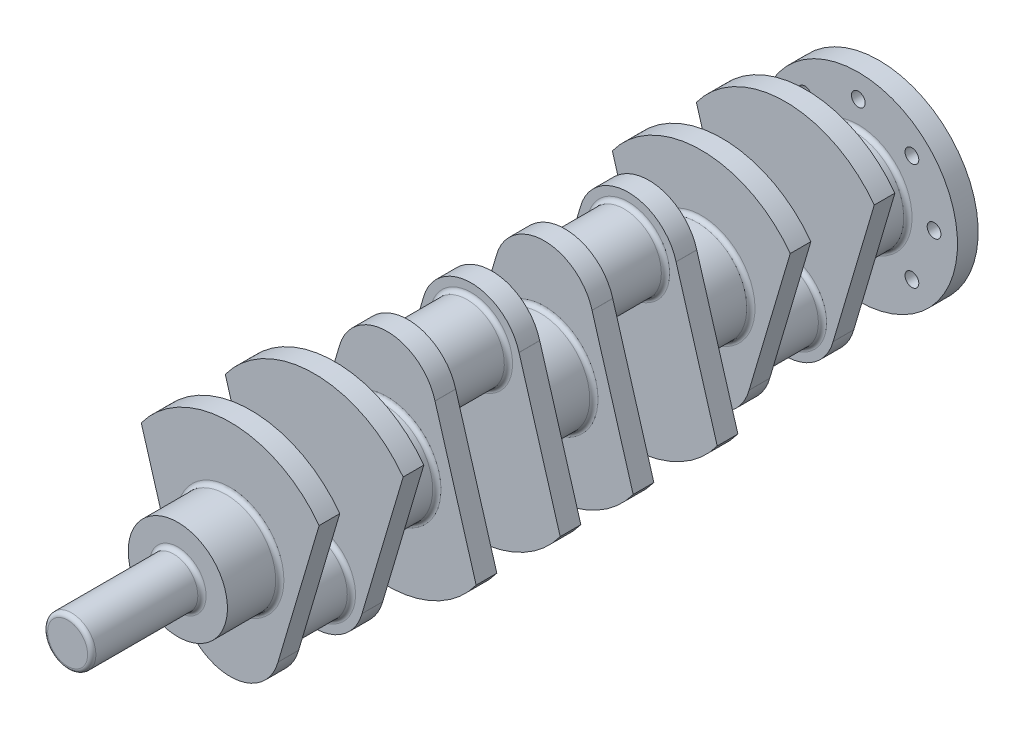
SolidWorks part; units mm, degrees
ref_plane "Front Plane" through (0, 0, 0) normal (0, 0, 1) x (1, 0, 0)
ref_plane "Top Plane" through (0, 0, 0) normal (0, 1, 0) x (1, 0, 0)
ref_plane "Right Plane" through (0, 0, 0) normal (1, 0, 0) x (0, 0, -1)
sketch "Sketch1" plane through (0, 0, 0) normal (0, 0, 1) x (1, 0, 0)
  line L0 (-840.1936, 0) -> (783.1901, 0) construction
  line L1 (0, 0) -> (0, -1117.6) construction
  line L2 (0, 0) -> (0, 1246.1176) construction
  line L3 (-1639.9655, 1199.8071) -> (-881.2738, -1361.4931)
  line L4 (1639.9655, 1199.8071) -> (881.2738, -1361.4931)
  circle A0 centre (0, -1117.6) radius 914.4
  arc A1 (-1639.9655, 1199.8071) -> (1639.9655, 1199.8071) centre (0, 0) cw
  dimension "D1" = 1828.8
  dimension "D3" = 2032
  dimension "D2" = 33
  dimension "D4" = 1117.6
extrude "Boss-Extrude1" add sketch "Sketch1" along normal blind 381 contours A0 | A1 L3 A0 L4
sketch "Sketch2" plane through (0, 0, 0) normal (0, 0, -1) x (-1, 0, 0)
  circle A0 centre (0, -1117.6) radius 685.8
  dimension "D1" = 1371.6
extrude "Boss-Extrude2" add sketch "Sketch2" along normal blind 1168.4
sketch "Sketch3" plane through (0, 0, 381) normal (0, 0, 1) x (1, 0, 0)
  circle A0 centre (0, 0) radius 914.4
  dimension "D1" = 1828.8
extrude "Boss-Extrude3" add sketch "Sketch3" along normal blind 965.2
ref_plane "Plane1" through (0, 0, -584.2) normal (0, 0, -1) x (-1, 0, 0)
mirror "Mirror2" about plane through (0, 0, -584.2) normal (0, 0, -1) of "Boss-Extrude1", "Boss-Extrude3"
ref_plane "Plane3" through (0, 0, -2032) normal (0, 0, -1) x (-1, 0, 0)
mirror "Mirror3" about plane through (0, 0, -2032) normal (0, 0, -1) of bodies 105
move or copy body "Body-Move/Copy1" bodies to move or copy 106 copy no rotation origin (0, 0, -3479.8) rotation axis (1, 0, 0) rotation angle 180
ref_plane "Plane4" through (0, 0, -4927.6) normal (0, 0, -1) x (-1, 0, 0)
mirror "Mirror5" about plane through (0, 0, -4927.6) normal (0, 0, -1) of bodies 105 107
sketch "Sketch4" plane through (0, 0, 1346.2) normal (0, 0, 1) x (1, 0, 0)
  circle A0 centre (0, 0) radius 444.5
  dimension "D1" = 889
extrude "Boss-Extrude4" add sketch "Sketch4" along normal blind 2032
sketch "Sketch5" plane through (0, 0, -11201.4) normal (0, 0, -1) x (-1, 0, 0)
  line L0 (0, 0) -> (0, 1397)
  circle A0 centre (0, 0) radius 1828.8
  circle A1 centre (0, 0) radius 1397 construction
  circle A2 centre (0, 1397) radius 127
  circle A3 centre (987.8282, 987.8282) radius 127
  circle A4 centre (1397, 0) radius 127
  circle A5 centre (987.8282, -987.8282) radius 127
  circle A6 centre (0, -1397) radius 127
  circle A7 centre (-987.8282, -987.8282) radius 127
  circle A8 centre (-1397, 0) radius 127
  circle A9 centre (-987.8282, 987.8282) radius 127
  circle A10 centre (0, 0) radius 914.4 construction
  point P22 (0, 0)
  dimension "D1" = 3657.6
  dimension "D2" = 2794
  dimension "D3" = 254
  dimension "D4" = 8
extrude "Boss-Extrude6" add sketch "Sketch5" along normal blind 381 separate body
combine bodies "Combine12" operation type add bodies to combine 111 107 110 109 113
fillet "Fillet2" radius 76.2 35 edges at (914.4, 0, -11201.4) (881.2738, -1361.4931, -8496.3) (-881.2738, -1361.4931, -8496.3) (-685.8, -1117.6, -8686.8) (-881.2738, -1361.4931, -10045.7) (881.2738, -1361.4931, -10045.7) (685.8, -1117.6, -9855.2) (914.4, 0, -10236.2) (881.2738, 1361.4931, -5600.7) (-881.2738, 1361.4931, -5600.7) (914.4, 0, -8305.8) (-685.8, 1117.6, -5791.2) (-881.2738, 1361.4931, -7150.1) (881.2738, 1361.4931, -7150.1) (685.8, 1117.6, -6959.6) (914.4, 0, -7340.6) (914.4, 0, -4445) (914.4, 0, -5410.2) (881.2738, 1361.4931, -4254.5) (-881.2738, 1361.4931, -4254.5) (-685.8, 1117.6, -4064) (-881.2738, 1361.4931, -2705.1) (881.2738, 1361.4931, -2705.1) (685.8, 1117.6, -2895.6) (914.4, 0, -2514.6) (914.4, 0, -1549.4) (881.2738, -1361.4931, -1358.9) (-881.2738, -1361.4931, -1358.9) (-685.8, -1117.6, -1168.4) (685.8, -1117.6, 0) (-881.2738, -1361.4931, 190.5) (881.2738, -1361.4931, 190.5) (914.4, 0, 381) (444.5, 0, 1346.2) (444.5, 0, 3378.2)
